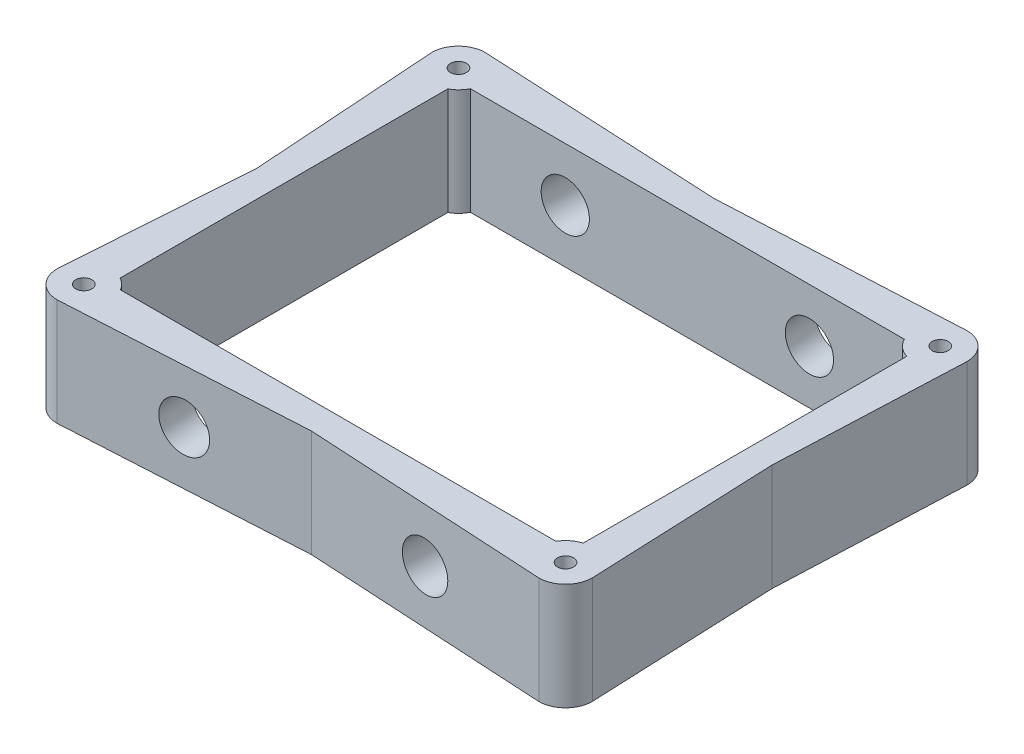
SolidWorks part; units mm, degrees
ref_plane "Front Plane" through (0, 0, 0) normal (0, 0, 1) x (1, 0, 0)
ref_plane "Top Plane" through (0, 0, 0) normal (0, 1, 0) x (1, 0, 0)
ref_plane "Right Plane" through (0, 0, 0) normal (1, 0, 0) x (0, 0, -1)
other "Center of Mass"
sketch "Sketch1" plane through (0, 0, 0) normal (0, 1, 0) x (1, 0, 0)
  line L0 (-45, 40) -> (0, 37.7582)
  line L1 (-40.6853, -32.4735) -> (40.6853, -32.4735)
  line L2 (-42.6109, -30.6077) -> (-42.6109, 30.6077)
  line L3 (-40.5307, 32.7582) -> (40.5307, 32.7582)
  line L4 (43.5292, -30.2212) -> (43.5292, 30.2212)
  line L5 (-45, -35) -> (45, 35) construction
  line L6 (-45, 35) -> (45, -35) construction
  line L7 (-50, 35) -> (-47.6109, 0)
  line L8 (-50, -35) -> (-47.6109, 0)
  line L9 (-45, -40) -> (0, -37.4735)
  line L10 (0, -37.4735) -> (45, -40)
  line L11 (50, -35) -> (48.5292, 0)
  line L12 (48.5292, 0) -> (50, 35)
  line L14 (45, 40) -> (0, 37.7582)
  arc A0 (-42.6109, 30.6077) -> (-40.5307, 32.7582) centre (-45, 35) ccw
  arc A1 (40.5307, 32.7582) -> (43.5292, 30.2212) centre (45, 35) ccw
  arc A2 (-40.6853, -32.4735) -> (-42.6109, -30.6077) centre (-45, -35) ccw
  arc A3 (45, -40) -> (49.9824, -34.5805) centre (45, -35) ccw
  arc A4 (-44.5031, 39.9752) -> (-49.9536, 34.3206) centre (-45, 35) ccw
  arc A5 (49.9824, 34.5805) -> (44.5031, 39.9752) centre (45, 35) ccw
  arc A6 (43.5292, -30.2212) -> (40.6853, -32.4735) centre (45, -35) ccw
  arc A7 (-49.9536, -34.3206) -> (-45, -40) centre (-45, -35) ccw
  circle A8 centre (45, 35) radius 1.5
  circle A9 centre (45, -35) radius 1.5
  circle A10 centre (-45, -35) radius 1.5
  circle A11 centre (-45, 35) radius 1.5
  point P0 (0, 0)
  point P31 (45, -35)
  point P34 (45, 35)
  point P35 (-45, 35)
  point P36 (-45, -35)
  dimension "D3" = 10
  dimension "D4" = 10
  dimension "D5" = 10
  dimension "D6" = 10
  dimension "D11" = 3
  dimension "D12" = 3
  dimension "D13" = 3
  dimension "D14" = 3
  dimension "D1" = 90
  dimension "D2" = 70
  dimension "D7" = 5
  dimension "D8" = 5
  dimension "D9" = 5
  dimension "D10" = 5
extrude "Boss-Extrude3" add sketch "Sketch1" along normal blind 20 contours L8 A7 L9 L10 A3 L11 L12 A5 L14 L0 A4 L7 A11 A10 A9 A8 L4 A6 L1 A2 L2 A0 L3 A1 region at (-44.8152, 0, -38.7086)
hole_wizard "M10x1.0 Tapped Hole2" positions "Sketch16" profile "Sketch15" tap size "M10x1.0" standard "ANSI Metric" end condition up to next
sketch "Sketch16" plane through (2.0973, 0, 37.3558) normal (0.0561, 0, 0.9984) x (0.9984, 0, -0.0561)
  line L0 (-47.1715, 20) -> (-2.1006, 20) construction
  line L1 (-24.6361, 20) -> (-24.6361, 0)
  line L2 (-47.1715, 0) -> (-2.1006, 0) construction
  point P12 (-24.6361, 10)
sketch "Sketch15" plane through (-22.5, 10, 38.7368) normal (0, 1, 0) x (0.9984, 0, -0.0561)
  line L0 (0, 0) -> (0, 6.2731)
  line L1 (0, 6.2731) -> (4.5, 6.2731)
  line L2 (4.5, 6.2731) -> (4.5, 0)
  line L5 (4.5, 0) -> (0, 0)
  line L11 (0, -6.35) -> (0, 107.95) construction
  dimension "Thru Tap Drill Dia." = 9
  dimension "Thru Tap Drill Depth" = 6.2731
cosmetic thread "Hole Thread16" parameters "D2"=10
hole_wizard "M10x1.0 Tapped Hole3" positions "Sketch20" profile "Sketch19" tap size "M10x1.0" standard "ANSI Metric" end condition up to next
sketch "Sketch20" plane through (-2.0973, 0, 37.3558) normal (-0.0561, 0, 0.9984) x (0.9984, 0, 0.0561)
  line L0 (24.6361, 20) -> (24.6361, 0)
  line L1 (2.1006, 20) -> (47.1715, 20) construction
  line L2 (2.1006, 0) -> (47.1715, 0) construction
  point P9 (24.6361, 10)
sketch "Sketch19" plane through (22.5, 10, 38.7368) normal (0, 1, 0) x (0.9984, 0, 0.0561)
  line L0 (0, 0) -> (0, 6.2731)
  line L1 (0, 6.2731) -> (4.5, 6.2731)
  line L2 (4.5, 6.2731) -> (4.5, 0)
  line L5 (4.5, 0) -> (0, 0)
  line L11 (0, -6.35) -> (0, 107.95) construction
  dimension "Thru Tap Drill Dia." = 9
  dimension "Thru Tap Drill Depth" = 6.2731
cosmetic thread "Hole Thread17" parameters "D2"=10
hole_wizard "M10x1.0 Tapped Hole4" positions "Sketch23" profile "Sketch22" tap size "M10x1.0" standard "ANSI Metric" end condition up to next
sketch "Sketch23" plane through (-1.8764, 0, -37.6647) normal (-0.0498, 0, -0.9988) x (-0.9988, 0, 0.0498)
  line L0 (-24.4066, 20) -> (-24.4066, 0)
  line L1 (-46.9345, 20) -> (-1.8787, 20) construction
  line L2 (-46.9345, 0) -> (-1.8787, 0) construction
  point P9 (-24.4066, 10)
sketch "Sketch22" plane through (22.5, 10, -38.8791) normal (0, 1, 0) x (-0.9988, 0, 0.0498)
  line L0 (0, 0) -> (0, 6.1285)
  line L1 (0, 6.1285) -> (4.5, 6.1285)
  line L2 (4.5, 6.1285) -> (4.5, 0)
  line L5 (4.5, 0) -> (0, 0)
  line L11 (0, -6.35) -> (0, 107.95) construction
  dimension "Thru Tap Drill Dia." = 9
  dimension "Thru Tap Drill Depth" = 6.1285
cosmetic thread "Hole Thread18" parameters "D2"=10
hole_wizard "M10x1.0 Tapped Hole5" positions "Sketch26" profile "Sketch25" tap size "M10x1.0" standard "ANSI Metric" end condition up to next
sketch "Sketch26" plane through (1.8764, 0, -37.6647) normal (0.0498, 0, -0.9988) x (-0.9988, 0, -0.0498)
  line L0 (24.4066, 20) -> (24.4066, 0)
  line L1 (46.9345, 20) -> (1.8787, 20) construction
  line L2 (46.9345, 0) -> (1.8787, 0) construction
  point P9 (24.4066, 10)
sketch "Sketch25" plane through (-22.5, 10, -38.8791) normal (0, 1, 0) x (-0.9988, 0, -0.0498)
  line L0 (0, 0) -> (0, 6.1285)
  line L1 (0, 6.1285) -> (4.5, 6.1285)
  line L2 (4.5, 6.1285) -> (4.5, 0)
  line L5 (4.5, 0) -> (0, 0)
  line L11 (0, -6.35) -> (0, 107.95) construction
  dimension "Thru Tap Drill Dia." = 9
  dimension "Thru Tap Drill Depth" = 6.1285
cosmetic thread "Hole Thread19" parameters "D2"=10
